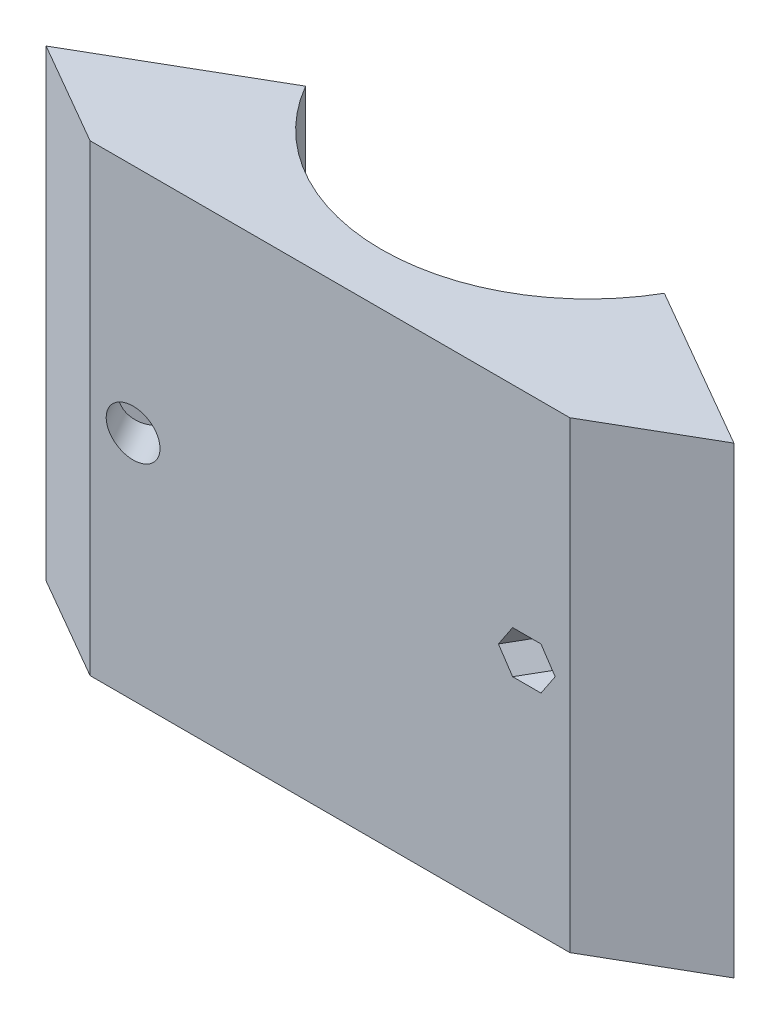
SolidWorks part; units mm, degrees
ref_plane "Front Plane" through (0, 0, 0) normal (0, 0, 1) x (1, 0, 0)
ref_plane "Top Plane" through (0, 0, 0) normal (0, 1, 0) x (1, 0, 0)
ref_plane "Right Plane" through (0, 0, 0) normal (1, 0, 0) x (0, 0, -1)
sketch "Sketch1" plane through (0, 0, 0) normal (0, 1, 0) x (1, 0, 0)
  line L20 (-84.8499, -19.3548) -> (-84.8499, -48.9881)
  line L21 (-84.8499, -48.9881) -> (-59.1867, -63.8048)
  line L22 (-59.1867, -63.8048) -> (59.1867, -63.8048)
  line L23 (59.1867, -63.8048) -> (84.8499, -48.9881)
  line L24 (84.8499, -48.9881) -> (84.8499, -19.3548)
  line L25 (84.8499, -19.3548) -> (25.6632, 83.1596)
  line L26 (25.6632, 83.1596) -> (0, 97.9763)
  line L27 (0, 97.9763) -> (-25.6632, 83.1596)
  line L28 (-25.6632, 83.1596) -> (-84.8499, -19.3548)
  line L29 (84.8499, -48.9881) -> (-55.2566, 31.9024)
  line L30 (55.2566, 31.9024) -> (-84.8499, -48.9881)
  line L31 (0, -63.8048) -> (0, 97.9763)
  circle A0 centre (0, 0) radius 51.1048
  point P13 (0, 0)
  point P20 (-44.2581, 25.5524)
  dimension "D1" = 102.2096
  dimension "D2" = 44.45
  dimension "D3" = 12.7
sketch "Sketch2" plane through (0, 0, 0) normal (0, 1, 0) x (1, 0, 0)
  line L0 (84.8499, -48.9881) -> (-55.2566, 31.9024) construction
  line L1 (59.1867, -63.8048) -> (84.8499, -48.9881) construction
  line L2 (-59.1867, -63.8048) -> (59.1867, -63.8048) construction
  line L3 (55.2566, 31.9024) -> (-84.8499, -48.9881) construction
  line L4 (-84.8499, -48.9881) -> (-59.1867, -63.8048) construction
  line L5 (84.8499, -48.9881) -> (-55.2566, 31.9024)
  line L6 (59.1867, -63.8048) -> (84.8499, -48.9881)
  line L7 (-59.1867, -63.8048) -> (59.1867, -63.8048)
  line L8 (55.2566, 31.9024) -> (-84.8499, -48.9881)
  line L9 (-84.8499, -48.9881) -> (-59.1867, -63.8048)
  line L10 (-64.0554, -36.9824) -> (-47.7703, -65.1891)
  line L13 (-54.0554, -54.3029) -> (-49.0757, -51.4279)
  line L14 (-49.0757, -51.4279) -> (-41.9299, -63.8048)
  line L15 (-41.9299, -63.8048) -> (-46.9096, -66.6798)
  line L16 (-46.9096, -66.6798) -> (-47.7703, -65.1891)
  line L17 (0, -55) -> (0, 55) construction
  line L21 (-64.0554, -36.9824) -> (-67.0865, -38.7324)
  line L22 (67.0865, -38.7324) -> (64.0554, -36.9824)
  line L23 (-46.9096, -66.6798) -> (-47.7703, -65.1891)
  line L24 (-61.0243, -35.2324) -> (-43.8785, -64.9298)
  line L25 (-61.0243, -35.2324) -> (-64.0554, -36.9824)
  circle A0 centre (0, 0) radius 51.1048 construction
  circle A1 centre (0, 0) radius 51.1048
  point P11 (-44.2581, -25.5524)
  dimension "D1" = 22.86
  dimension "D3" = 5.75
  dimension "D4" = 20
  dimension "D2" = 3.5
extrude "Boss-Extrude1" add sketch "Sketch1" along normal mid plane 114.3 contours A0 L30 L21 L22 L31 | A0 L31 L22 L23 L29 region at (-42.3912, 0, 50.0899) region at (42.3912, 0, 50.0899)
revolve "Cut-Revolve7" cut sketch "Sketch2" angle 360 about L10 region at (-46.2293, 0, 64.8686) region at (-49.4946, 0, 58.6041) region at (-57.5399, 0, 44.7677)
revolve "Cut-Revolve8" cut sketch "Sketch2<7>" angle 360 about L10 region at (-46.6215, 0, 57.8931)
sketch "Sketch2<7>" plane through (0, 0, 0) normal (0, 1, 0) x (1, 0, 0) same geometry as "Sketch2"
mirror "Mirror1" about plane through (0, 0, 0) normal (1, 0, 0) of "Cut-Revolve7"
sketch "Sketch3" plane through (0, 0, 0) normal (0.5, 0, -0.866) x (-0.866, 0, -0.5)
  line L1 (-76.9959, 5.25) -> (-80.027, 0)
  line L2 (-80.027, 0) -> (-76.9959, -5.25)
  line L3 (-76.9959, -5.25) -> (-70.9337, -5.25)
  line L4 (-70.9337, -5.25) -> (-67.9026, 0)
  line L5 (-67.9026, 0) -> (-70.9337, 5.25)
  line L6 (-70.9337, 5.25) -> (-76.9959, 5.25)
  circle A0 centre (-73.9648, 0) radius 3.5 construction
  circle A1 centre (-73.9648, 0) radius 3.5
  circle A2 centre (-73.9648, 0) radius 5.25 construction
  dimension "D1" = 10.5
extrude "Cut-Extrude1" cut sketch "Sketch3" against normal through all from offset 16 offset against normal yes
ref_axis "Axis1" through (0, 57.15, 0) along (0, -1, 0)
equation "\"Tube_Diameter_With_Tolerance\"= 4.024"
equation "\"Vertical_Surface_Height\"= 1.75in"
equation "\"D1@Sketch1\"=\"Tube_Diameter_With_Tolerance\""
equation "\"D2@Sketch1\"=\"Vertical_Surface_Height\""
equation "\"Offset_From_Diameter\"= .5in"
equation "\"D3@Sketch1\"=\"Offset_From_Diameter\""
equation "\"Thread_Center\"= 1.8 * \"Offset_From_Diameter\""
equation "\"M6_Thread_Clearance\"= 7mm"
equation "\"M6_Head_Clearance\"= 11.5mm"
equation "\"M6_Nut_Flat_To_Flat\"= 10.5mm"
equation "\"Nut_Start\"= 16mm"
equation "\"D1@Sketch2\"=\"Thread_Center\""
equation "\"D3@Sketch2\"=\"M6_Head_Clearance\"/2"
equation "\"D4@Sketch2\"=\"Screw_Head_Start\""
equation "\"Length\"= 4.5in"
equation "\"D1@Boss-Extrude1\"=\"Length\""
equation "\"D2@Sketch2\"=\"M6_Thread_Clearance\"/2"
equation "\"D1@Sketch3\"=\"M6_Nut_Flat_To_Flat\""
equation "\"D19@Cut-Extrude1\"=\"Nut_Start\""
equation "\"Screw_Head_Start\"= 20mm"
